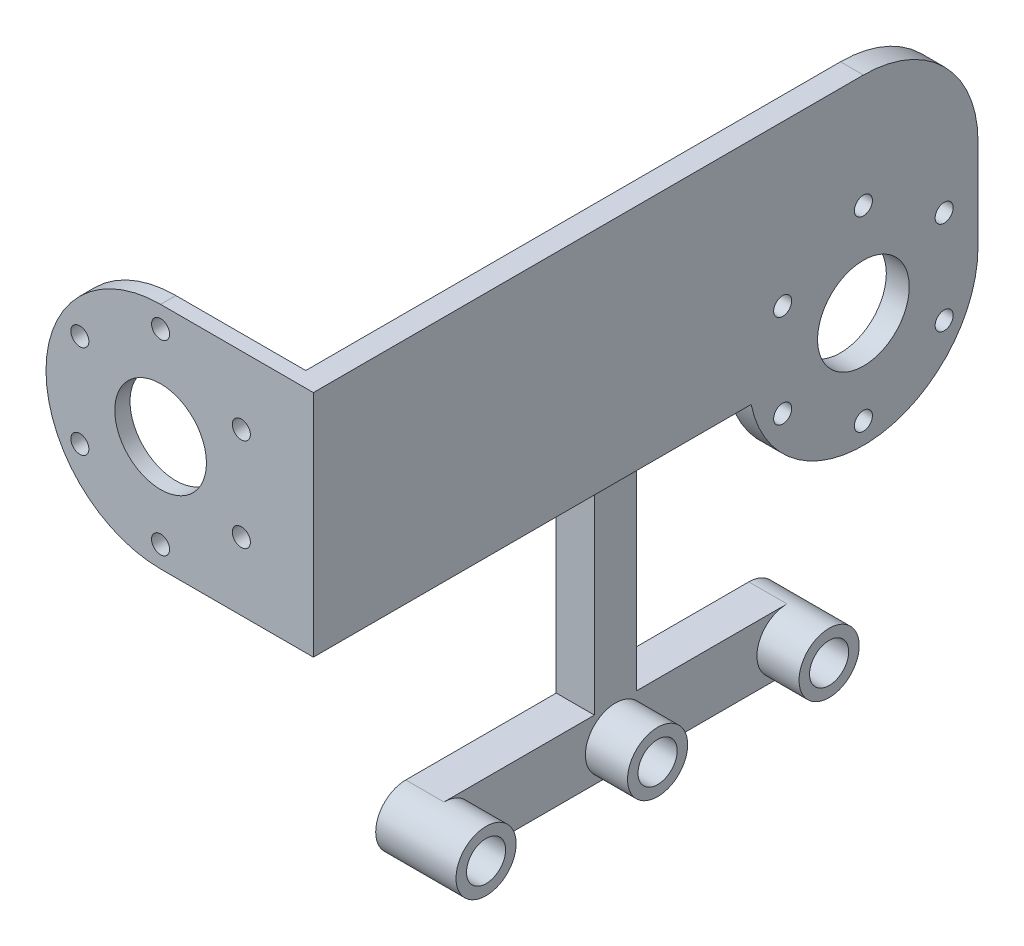
SolidWorks part; units mm, degrees
ref_plane "Front Plane" through (0, 0, 0) normal (0, 0, 1) x (1, 0, 0)
ref_plane "Top Plane" through (0, 0, 0) normal (0, 1, 0) x (1, 0, 0)
ref_plane "Right Plane" through (0, 0, 0) normal (1, 0, 0) x (0, 0, -1)
sketch "Sketch1" plane through (0, 0, 0) normal (0, 0, 1) x (1, 0, 0)
  line L1 (-25.4, -19.05) -> (25.4, -19.05)
  line L2 (-25.4, -19.05) -> (-25.4, 19.05)
  line L3 (-25.4, 19.05) -> (25.4, 19.05)
  line L4 (25.4, -19.05) -> (25.4, 19.05)
  line L5 (-25.4, -19.05) -> (25.4, 19.05) construction
  line L6 (-25.4, 19.05) -> (25.4, -19.05) construction
  circle A0 centre (0, 0) radius 15.5 construction
  circle A1 centre (0, 15.5) radius 1.5
  circle A2 centre (13.4234, 7.75) radius 1.5
  circle A3 centre (13.4234, -7.75) radius 1.5
  circle A4 centre (0, -15.5) radius 1.5
  circle A5 centre (-13.4234, -7.75) radius 1.5
  circle A6 centre (-13.4234, 7.75) radius 1.5
  circle A7 centre (0, 0) radius 7.62
  point P0 (0, 0)
  point P22 (0, 0)
  dimension "D2" = 31
  dimension "D3" = 3
  dimension "D5" = 15.24
  dimension "D1" = 38.1
  dimension "D6" = 50.8
  dimension "D4" = 6
extrude "Boss-Extrude1" add sketch "Sketch1" along normal blind 2.54
sketch "Sketch2" plane through (0, 0, 2.54) normal (0, 0, 1) x (1, 0, 0)
  line L0 (25.4, 19.05) -> (-25.4, 19.05) construction
  line L1 (-25.4, -19.05) -> (25.4, -19.05) construction
  line L2 (0, 19.05) -> (-25.4, 19.05)
  line L3 (-25.4, 19.05) -> (-25.4, -19.05)
  line L4 (-25.4, 19.05) -> (-25.4, -19.05) construction
  line L5 (-25.4, -19.05) -> (0, -19.05)
  arc A0 (0, 19.05) -> (0, -19.05) centre (0, 0) ccw
extrude "Cut-Extrude1" cut sketch "Sketch2" against normal up to next
sketch "Sketch4" plane through (25.4, 0, 0) normal (1, 0, 0) x (0, 0, -1)
  line L0 (-2.54, -19.05) -> (0, -19.05) construction
  line L1 (-2.54, 19.05) -> (88.9, 19.05)
  line L2 (-2.54, 19.05) -> (-2.54, -19.05)
  line L3 (-2.54, -19.05) -> (88.9, -19.05)
  line L4 (88.9, 19.05) -> (88.9, -19.05)
  line L5 (0, -19.05) -> (0, 19.05) construction
  line L7 (107.95, 0) -> (69.85, 0)
  line L8 (107.95, 0) -> (107.95, -15.24)
  line L9 (107.95, -15.24) -> (69.85, -15.24)
  line L10 (69.85, 0) -> (69.85, -15.24)
  circle A0 centre (88.9, 0) radius 19.05
  circle A1 centre (88.9, -15.24) radius 19.05
  dimension "D1" = 88.9
  dimension "D2" = 15.24
extrude "Boss-Extrude2" add sketch "Sketch4" against normal blind 3.81 contours L2 L1 L4 L3 | A0 | L8 L7 L10 L9 | A1
sketch "Sketch5" plane through (25.4, 0, 0) normal (1, 0, 0) x (0, 0, -1)
  circle A0 centre (88.9, -15.24) radius 7.62
  circle A2 centre (88.9, -15.24) radius 15.5 construction
  circle A3 centre (88.9, 0.26) radius 1.5
  circle A4 centre (102.3234, -7.49) radius 1.5
  circle A5 centre (102.3234, -22.99) radius 1.5
  circle A6 centre (88.9, -30.74) radius 1.5
  circle A7 centre (75.4766, -22.99) radius 1.5
  circle A8 centre (75.4766, -7.49) radius 1.5
  arc A9 (70.2349, -19.05) -> (107.95, -15.24) centre (88.9, -15.24) ccw construction
  dimension "D1" = 15.24
  dimension "D2" = 31
  dimension "D3" = 3
  dimension "D4" = 6
extrude "Cut-Extrude2" cut sketch "Sketch5" against normal up to next
sketch "Sketch6" plane through (0, -19.05, 0) normal (0, -1, 0) x (1, 0, 0)
  line L0 (25.4, 2.54) -> (25.4, -70.2349) construction
  line L1 (25.4, -56.8849) -> (6.35, -56.8849)
  line L2 (25.4, -56.8849) -> (25.4, -63.8849)
  line L3 (25.4, -63.8849) -> (6.35, -63.8849)
  line L4 (6.35, -56.8849) -> (6.35, -63.8849)
  line L5 (25.4, -70.2349) -> (21.59, -70.2349) construction
  dimension "D1" = 7
  dimension "D2" = 19.05
  dimension "D3" = 6.35
extrude "Boss-Extrude3" add sketch "Sketch6" against normal blind 6.35
sketch "Sketch9" plane through (6.35, 0, 0) normal (-1, 0, 0) x (0, 0, 1)
  line L0 (-56.8849, -12.7) -> (-56.8849, -19.05) construction
  line L1 (-63.8849, -19.05) -> (-56.8849, -19.05)
  line L2 (-63.8849, -19.05) -> (-63.8849, -63.45)
  line L3 (-88.9, -73.45) -> (-31.8698, -73.45)
  line L4 (-56.8849, -19.05) -> (-56.8849, -63.45)
  line L5 (-60.3849, -19.05) -> (-60.3849, -73.45) construction
  line L6 (-88.9, -7.62) -> (-88.9, -22.86) construction
  line L7 (-56.8849, -63.45) -> (-31.8698, -63.45)
  line L8 (-60.3849, -63.45) -> (-60.3849, -73.45)
  line L9 (-60.3849, -73.45) -> (-31.8698, -73.45)
  line L11 (-63.8849, -63.45) -> (-88.9, -63.45)
  line L12 (-60.3849, -63.45) -> (-60.3849, -73.45)
  line L13 (-60.3849, -73.45) -> (-88.9, -73.45)
  circle A0 centre (-88.9, -15.24) radius 7.62 construction
  circle A1 centre (-60.3849, -68.45) radius 5 construction
  circle A2 centre (-60.3849, -68.45) radius 3.25
  arc A3 (-88.9, -63.45) -> (-88.9, -73.45) centre (-88.9, -68.45) ccw
  circle A4 centre (-88.9, -68.45) radius 3.25
  circle A5 centre (-31.8698, -68.45) radius 3.25
  arc A6 (-31.8698, -63.45) -> (-31.8698, -73.45) centre (-31.8698, -68.45) cw
  point P23 (-32.6563, -63.45)
  point P27 (0, 0)
  point P28 (-88.9, -63.45)
  point P30 (0, 0)
  point P32 (-88.9, -64.2835)
  point P33 (0, 0)
  point P34 (-64.4134, -73.45)
  point P35 (0, 0)
  point P36 (-88.5388, -73.45)
  line M5 (-63.8849, -19.05) -> (-56.8849, -19.05)
  dimension "D2" = 10
  dimension "D3" = 6.5
  dimension "D1" = 58.21
extrude "Boss-Extrude6" add sketch "Sketch9" against normal blind 6.35 contours A6 L7 L4 L2 L11 A3 L3 A2 A4 A5 M5 region at (6.35, -58.6211, -60.3849)
sketch "Sketch10" plane through (12.7, 0, 0) normal (1, 0, 0) x (0, 0, -1)
  line L1 (60.3849, -19.05) -> (60.3849, -73.45) construction
  line L3 (63.8849, -63.45) -> (88.9, -63.45) construction
  line L4 (63.8849, -19.05) -> (56.8849, -19.05) construction
  circle A0 centre (60.3849, -68.45) radius 5
  circle A2 centre (60.3849, -68.45) radius 5 construction
  circle A4 centre (60.3849, -68.45) radius 3.25
  circle A5 centre (60.3849, -68.45) radius 3.25 construction
  circle A6 centre (31.8698, -68.45) radius 5
  circle A7 centre (88.9, -68.45) radius 5
  circle A8 centre (88.9, -68.45) radius 3.25 construction
  circle A9 centre (31.8698, -68.45) radius 3.25 construction
  circle A10 centre (88.9, -68.45) radius 3.25
  circle A11 centre (31.8698, -68.45) radius 3.25
  arc A12 (31.8698, -63.45) -> (31.8698, -73.45) centre (31.8698, -68.45) ccw construction
  arc A13 (88.9, -73.45) -> (88.9, -63.45) centre (88.9, -68.45) ccw construction
  point P6 (60.3849, -19.05)
extrude "Boss-Extrude7" add sketch "Sketch10" along normal blind 7 contours A6 | A11 | A4 | A0 | A10 | A7
equation "\"mounting distance\" = 24mm"
equation "\"ded\"= 2mm"
equation "\"rack base distance\"= 3mm"
equation "\"slot depth\"= 1.15in"
equation "\"stand height\"= \"mounting distance\" + \"ded\" + \"rack base distance\" + \"slot depth\""
equation "\"D1@Sketch9\"=\"stand height\""
